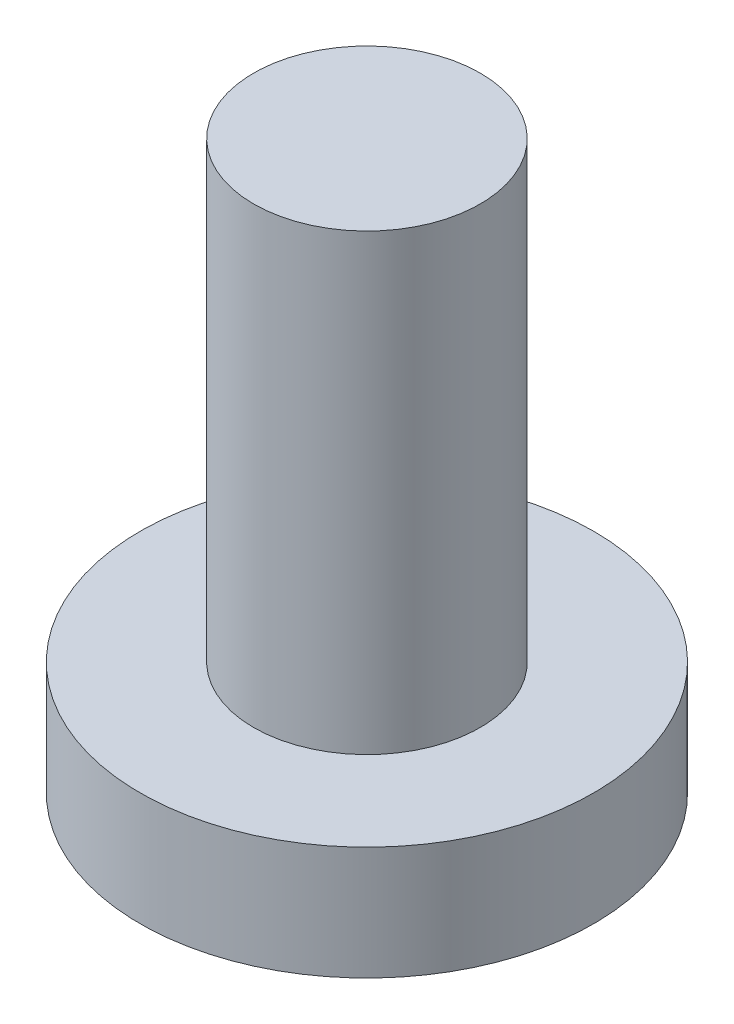
SolidWorks part; units mm, degrees
ref_plane "Front Plane" through (0, 0, 0) normal (0, 0, 1) x (1, 0, 0)
ref_plane "Top Plane" through (0, 0, 0) normal (0, 1, 0) x (1, 0, 0)
ref_plane "Right Plane" through (0, 0, 0) normal (1, 0, 0) x (0, 0, -1)
sketch "Sketch1" plane through (0, 0, 0) normal (0, 0, 1) x (1, 0, 0)
  line L0 (0, -3.3671) -> (0, 12.9367) construction
  line L1 (0, 0) -> (4, 0)
  line L2 (4, 0) -> (4, 2)
  line L3 (4, 2) -> (2, 2)
  line L4 (2, 2) -> (2, 10)
  line L5 (2, 10) -> (0, 10)
  line L6 (0, 10) -> (0, 0)
  line L7 (0, 0) -> (0.0506, -0.0253)
  dimension "D1" = 2
  dimension "D2" = 4
  dimension "D3" = 2
  dimension "D4" = 8
revolve "Revolve1" add sketch "Sketch1" angle 360 about L0 region at (1.3333, 4.3333, 0)
